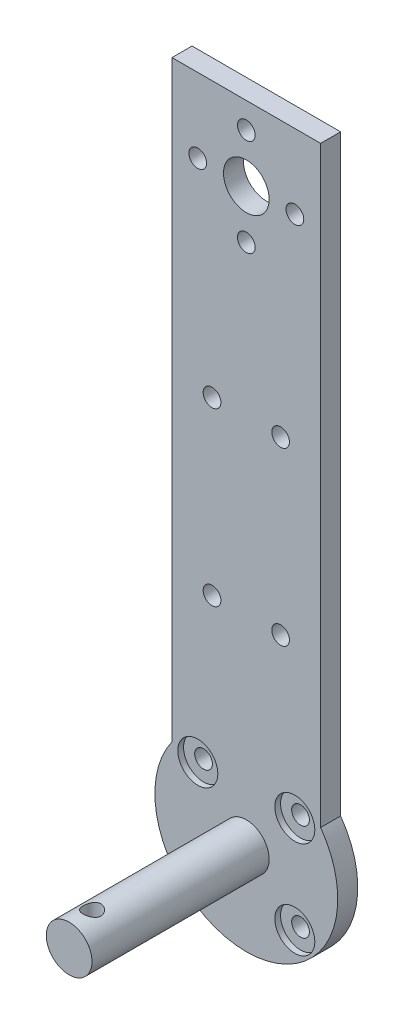
SolidWorks part; units mm, degrees
ref_plane "Front Plane" through (0, 0, 0) normal (0, 0, 1) x (1, 0, 0)
ref_plane "Top Plane" through (0, 0, 0) normal (0, 1, 0) x (1, 0, 0)
ref_plane "Right Plane" through (0, 0, 0) normal (1, 0, 0) x (0, 0, -1)
sketch "Sketch1" plane through (0, 0, 0) normal (0, 0, 1) x (1, 0, 0)
  line L0 (13, 113) -> (13, 9.3274)
  line L2 (13, 113) -> (-13, 113)
  line L4 (0, 0) -> (8.4853, 8.4853) construction
  line L5 (0, 0) -> (0, 100) construction
  line L6 (0, 0) -> (0, 35) construction
  line L7 (6, 35) -> (-6, 35) construction
  line L8 (0, 100) -> (0, 65) construction
  line L9 (-6, 65) -> (6, 65) construction
  line L10 (-13, 113) -> (-13, 9.3274)
  circle A2 centre (0, 0) radius 12 construction
  circle A3 centre (8.4853, 8.4853) radius 1.55
  circle A4 centre (8.4853, -8.4853) radius 1.55
  circle A5 centre (-8.4853, -8.4853) radius 1.55
  circle A6 centre (-8.4853, 8.4853) radius 1.55
  circle A7 centre (0, 0) radius 4 construction
  circle A8 centre (0, 100) radius 4
  circle A9 centre (0, 100) radius 8.5 construction
  circle A10 centre (0, 108.5) radius 1.55
  circle A11 centre (8.5, 100) radius 1.55
  circle A12 centre (0, 91.5) radius 1.55
  circle A13 centre (-8.5, 100) radius 1.55
  circle A14 centre (6, 65) radius 1.55
  circle A15 centre (6, 35) radius 1.55
  circle A16 centre (-6, 65) radius 1.55
  circle A17 centre (-6, 35) radius 1.55
  circle A19 centre (0, 0) radius 16 construction
  arc A20 (-13, 9.3274) -> (13, 9.3274) centre (0, 0) ccw
  point P6 (0, 0)
  point P19 (0, 0)
  point P31 (0, 100)
  point P33 (0, 35)
  point P38 (0, 65)
  dimension "D1" = 4
  dimension "D2" = 4
extrude "Boss-Extrude1" add sketch "Sketch1" along normal blind 3.5
sketch "Sketch2" plane through (0, 0, 3.5) normal (0, 0, 1) x (1, 0, 0)
  circle A0 centre (0, 0) radius 4
extrude "Boss-Extrude2" add sketch "Sketch2" along normal blind 31
sketch "Sketch3" plane through (0, 0, 3.5) normal (0, 0, 1) x (1, 0, 0)
  circle A0 centre (-8.4853, 8.4853) radius 3.5
  circle A4 centre (8.4853, 8.4853) radius 3.5
  circle A5 centre (8.4853, -8.4853) radius 3.5
  circle A6 centre (-8.4853, -8.4853) radius 3.5
  point P12 (0, 0)
extrude "Cut-Extrude1" cut sketch "Sketch3" against normal blind 1
ref_axis "Axis1" through (0, 0, 34.5) along (0, 0, -1)
ref_plane "Plane1" through (0, 0, 0) normal (0, -1, 0) x (0, 0, -1)
sketch "Sketch4" plane through (0, 0, 0) normal (0, -1, 0) x (0, 0, -1)
  line L0 (-34.5, 0) -> (-30.5, 0) construction
  line L1 (-34.5, 4) -> (-34.5, -4) construction
  line L2 (-34.5, 0) -> (-3.5, 0) construction
  circle A0 centre (-30.5, 0) radius 1.55
extrude "Cut-Extrude2" cut sketch "Sketch4" against normal up to surface and the other way up to surface up to face at (4, 0, 34.5) other way up to face at (4, 0, 34.5)
